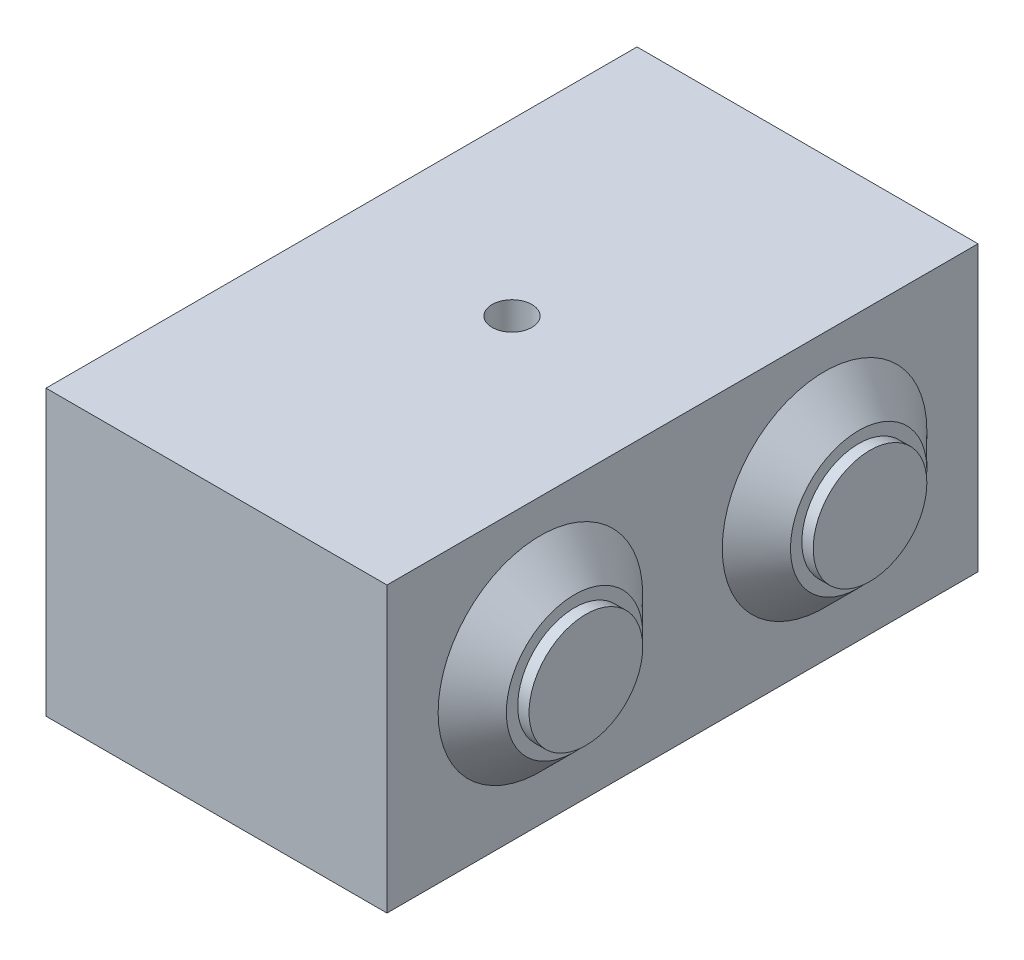
SolidWorks part; units mm, degrees
ref_plane "Front Plane" through (0, 0, 0) normal (0, 0, 1) x (1, 0, 0)
ref_plane "Top Plane" through (0, 0, 0) normal (0, 1, 0) x (1, 0, 0)
ref_plane "Right Plane" through (0, 0, 0) normal (1, 0, 0) x (0, 0, -1)
sketch "Sketch1" plane through (0, 0, 0) normal (0, 1, 0) x (1, 0, 0)
  line L1 (0, 0) -> (30, 0)
  line L2 (0, 0) -> (0, 52)
  line L3 (0, 52) -> (30, 52)
  line L4 (30, 0) -> (30, 52)
  dimension "D1" = 30
  dimension "D2" = 52
extrude "Boss-Extrude1" add sketch "Sketch1" along normal blind 25
sketch "Sketch2" plane through (30, 0, 0) normal (1, 0, 0) x (0, 0, -1)
  line L0 (0, 25) -> (0, 0) construction
  circle A0 centre (13.5, 13.0219) radius 9
  circle A1 centre (38.5, 13.0219) radius 9
  dimension "D1" = 18
  dimension "D2" = 18
  dimension "D3" = 25
  dimension "D4" = 13.5
extrude "Boss-Extrude2" add sketch "Sketch2" along normal blind 3
chamfer "Chamfer1" distance 3 angle 45 2 edges at (33, 13.0219, -47.5) (33, 13.0219, -22.5)
sketch "Sketch3" plane through (33, 0, 0) normal (1, 0, 0) x (0, 0, -1)
  circle A0 centre (38.5, 13.0219) radius 5
  circle A1 centre (13.5, 13.0219) radius 5
  dimension "D1" = 10
  dimension "D2" = 10
extrude "Boss-Extrude3" add sketch "Sketch3" along normal blind 1
sketch "Sketch4" plane through (0, 0, 0) normal (0, -1, 0) x (1, 0, 0)
  line L0 (0, 0) -> (30, -52) construction
  circle A0 centre (15, -26) radius 1.75
  dimension "D1" = 3.5
extrude "Cut-Extrude1" cut sketch "Sketch4" against normal through all
